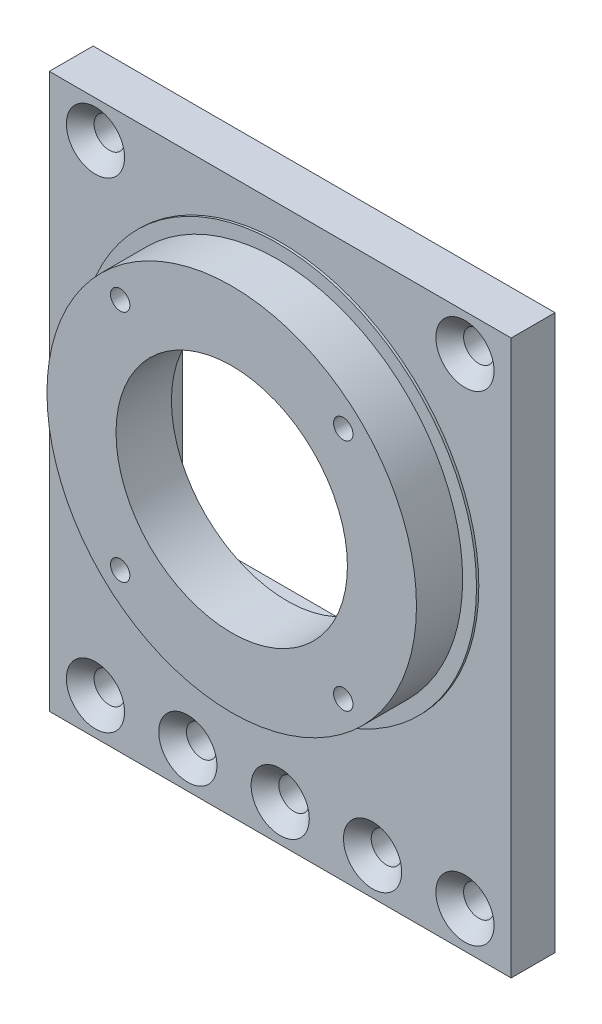
SolidWorks part; units mm, degrees
material "PVC rigide"
ref_plane "Plan de face" through (0, 0, 0) normal (0, 0, 1) x (1, 0, 0)
ref_plane "Plan de dessus" through (0, 0, 0) normal (0, 1, 0) x (1, 0, 0)
ref_plane "Plan de droite" through (0, 0, 0) normal (1, 0, 0) x (0, 0, -1)
sketch "Esquisse1" plane through (0, 0, 0) normal (0, 0, 1) x (1, 0, 0)
  line L1 (28, 28) -> (-28, 28)
  line L2 (28, 28) -> (28, -28)
  line L3 (28, -28) -> (-28, -28)
  line L4 (-28, 28) -> (-28, -28)
  line L5 (28, 28) -> (-28, -28) construction
  line L6 (28, -28) -> (-28, 28) construction
  line L7 (50, 50) -> (-50, 50)
  line L8 (50, 50) -> (50, -50)
  line L9 (50, -50) -> (-50, -50)
  line L10 (-50, 50) -> (-50, -50)
  line L11 (50, 50) -> (-50, -50) construction
  line L12 (50, -50) -> (-50, 50) construction
  circle A0 centre (0, 0) radius 40 construction
  point P0 (0, 0)
  dimension "D2" = 80
  dimension "D1" = 56
  dimension "D3" = 100
extrude "Boss.-Extru.1" add sketch "Esquisse1" along normal blind 10
fillet "Congé1" radius 3.5 4 edges at (-28, -28, 5) (28, 28, 5) (-28, 28, 5) (28, -28, 5)
sketch "Esquisse3" plane through (0, 0, 10) normal (0, 0, 1) x (1, 0, 0)
  line L5 (-28, 24.5) -> (-28, -24.5)
  line L6 (24.5, 28) -> (-24.5, 28)
  line L7 (28, -24.5) -> (28, 24.5)
  line L8 (-24.5, -28) -> (24.5, -28)
  line L9 (-28, 24.5) -> (-28, -24.5)
  line L10 (24.5, 28) -> (-24.5, 28)
  line L11 (28, -24.5) -> (28, 24.5)
  line L12 (-24.5, -28) -> (24.5, -28)
  circle A0 centre (0, 0) radius 40
  arc A5 (-24.5, 28) -> (-28, 24.5) centre (-24.5, 24.5) ccw
  arc A6 (28, 24.5) -> (24.5, 28) centre (24.5, 24.5) ccw
  arc A7 (24.5, -28) -> (28, -24.5) centre (24.5, -24.5) ccw
  arc A8 (-28, -24.5) -> (-24.5, -28) centre (-24.5, -24.5) ccw
  arc A9 (-24.5, 28) -> (-28, 24.5) centre (-24.5, 24.5) ccw
  arc A10 (28, 24.5) -> (24.5, 28) centre (24.5, 24.5) ccw
  arc A11 (24.5, -28) -> (28, -24.5) centre (24.5, -24.5) ccw
  arc A12 (-28, -24.5) -> (-24.5, -28) centre (-24.5, -24.5) ccw
  dimension "D1" = 80
  dimension "D2" = 0
extrude "Boss.-Extru.2" add sketch "Esquisse3" along normal blind 10
sketch "Esquisse4" plane through (0, 0, 10) normal (0, 0, 1) x (1, 0, 0)
  circle A0 centre (0, 0) radius 43
  circle A1 centre (0, 0) radius 40 construction
  dimension "D1" = 3
extrude "Enlèv. mat.-Extru.2" cut sketch "Esquisse4" against normal blind 0.5 flip side to cut
sketch "Esquisse5" plane through (0, 0, 0) normal (0, 0, -1) x (-1, 0, 0)
  line L1 (30.65, -30.65) -> (-30.65, -30.65)
  line L2 (30.65, -30.65) -> (30.65, 30.65)
  line L3 (30.65, 30.65) -> (-30.65, 30.65)
  line L4 (-30.65, -30.65) -> (-30.65, 30.65)
  line L5 (30.65, -30.65) -> (-30.65, 30.65) construction
  line L6 (30.65, 30.65) -> (-30.65, -30.65) construction
  point P0 (0, 0)
  dimension "D1" = 61.3
extrude "Enlèv. mat.-Extru.3" cut sketch "Esquisse5" against normal blind 9
sketch "Esquisse6" plane through (0, 0, 9) normal (0, 0, -1) x (-1, 0, 0)
  line L4 (-30.65, 30.65) -> (-30.65, -30.65)
  line L5 (-30.65, -30.65) -> (30.65, -30.65)
  line L6 (30.65, -30.65) -> (30.65, 30.65)
  line L7 (30.65, 30.65) -> (-30.65, 30.65)
  line L8 (-30.65, 30.65) -> (-30.65, -30.65)
  line L9 (-30.65, -30.65) -> (30.65, -30.65)
  line L10 (30.65, -30.65) -> (30.65, 30.65)
  line L11 (30.65, 30.65) -> (-30.65, 30.65)
  line L13 (28, -24.5) -> (28, 24.5)
  line L14 (-24.5, -28) -> (24.5, -28)
  line L15 (-28, 24.5) -> (-28, -24.5)
  line L16 (24.5, 28) -> (-24.5, 28)
  line L17 (28, -24.5) -> (28, 24.5)
  line L18 (-24.5, -28) -> (24.5, -28)
  line L19 (-28, 24.5) -> (-28, -24.5)
  line L20 (24.5, 28) -> (-24.5, 28)
  arc A4 (28, 24.5) -> (24.5, 28) centre (24.5, 24.5) ccw
  arc A5 (24.5, -28) -> (28, -24.5) centre (24.5, -24.5) ccw
  arc A6 (-28, -24.5) -> (-24.5, -28) centre (-24.5, -24.5) ccw
  arc A7 (-24.5, 28) -> (-28, 24.5) centre (-24.5, 24.5) ccw
  arc A8 (28, 24.5) -> (24.5, 28) centre (24.5, 24.5) ccw
  arc A9 (24.5, -28) -> (28, -24.5) centre (24.5, -24.5) ccw
  arc A10 (-28, -24.5) -> (-24.5, -28) centre (-24.5, -24.5) ccw
  arc A11 (-24.5, 28) -> (-28, 24.5) centre (-24.5, 24.5) ccw
  dimension "D1" = 0
  dimension "D2" = 0
extrude "Boss.-Extru.3" add sketch "Esquisse6" along normal blind 1
sketch "Esquisse12" plane through (0, -50, 0) normal (0, -1, 0) x (1, 0, 0)
  line L4 (50, 9.5) -> (-50, 9.5)
  line L5 (-50, 9.5) -> (-50, 0)
  line L6 (-50, 0) -> (50, 0)
  line L7 (50, 0) -> (50, 9.5)
  line L8 (50, 9.5) -> (-50, 9.5)
  line L9 (-50, 9.5) -> (-50, 0)
  line L10 (-50, 0) -> (50, 0)
  line L11 (50, 0) -> (50, 9.5)
  dimension "D1" = 0
extrude "Boss.-Extru.5" add sketch "Esquisse12" along normal blind 20
sketch "Esquisse7" plane through (0, 0, 8) normal (0, 0, -1) x (-1, 0, 0)
  line L5 (-24.5, -28) -> (24.5, -28)
  line L6 (28, -24.5) -> (28, 24.5)
  line L7 (24.5, 28) -> (-24.5, 28)
  line L8 (-28, 24.5) -> (-28, -24.5)
  line L9 (-24.5, -28) -> (24.5, -28)
  line L10 (28, -24.5) -> (28, 24.5)
  line L11 (24.5, 28) -> (-24.5, 28)
  line L12 (-28, 24.5) -> (-28, -24.5)
  circle A0 centre (0, 0) radius 25.05
  arc A5 (24.5, -28) -> (28, -24.5) centre (24.5, -24.5) ccw
  arc A6 (28, 24.5) -> (24.5, 28) centre (24.5, 24.5) ccw
  arc A7 (-24.5, 28) -> (-28, 24.5) centre (-24.5, 24.5) ccw
  arc A8 (-28, -24.5) -> (-24.5, -28) centre (-24.5, -24.5) ccw
  arc A9 (24.5, -28) -> (28, -24.5) centre (24.5, -24.5) ccw
  arc A10 (28, 24.5) -> (24.5, 28) centre (24.5, 24.5) ccw
  arc A11 (-24.5, 28) -> (-28, 24.5) centre (-24.5, 24.5) ccw
  arc A12 (-28, -24.5) -> (-24.5, -28) centre (-24.5, -24.5) ccw
  dimension "D1" = 50.1
  dimension "D2" = 0
extrude "Boss.-Extru.4" add sketch "Esquisse7" against normal up to surface (12 mm away) up to face at (40, 0, 20)
sketch "Esquisse10" plane through (0, 0, 8) normal (0, 0, -1) x (-1, 0, 0)
  line L1 (-24.1504, -25.3329) -> (24.1504, -25.3329) construction
  line L2 (-24.1504, -25.3329) -> (-24.1504, 25.3329) construction
  line L3 (-24.1504, 25.3329) -> (24.1504, 25.3329) construction
  line L4 (24.1504, -25.3329) -> (24.1504, 25.3329) construction
  line L5 (-24.1504, -25.3329) -> (24.1504, 25.3329) construction
  line L6 (-24.1504, 25.3329) -> (24.1504, -25.3329) construction
  circle A0 centre (0, 0) radius 35 construction
  point P0 (0, 0)
  dimension "D1" = 70
hole_wizard "Trou taraudé M5x0.81" positions "Esquisse3D2" profile "Esquisse11" tap size "M5x0.8" standard "Ansi Metric" end condition through all
sketch3d "Esquisse3D2"
  point P0 (24.1504, 25.3329, 8)
  point P3 (24.1504, -25.3329, 8)
  point P6 (-24.1504, 25.3329, 8)
  point P9 (-24.1504, -25.3329, 8)
sketch "Esquisse11" plane through (24.1504, 25.3329, 8) normal (1, 0, 0) x (0, 1, 0)
  line L0 (0, 0) -> (0, 12)
  line L1 (0, 12) -> (2.1, 12)
  line L2 (2.1, 12) -> (2.1, 0)
  line L5 (2.1, 0) -> (0, 0)
  line L11 (0, -6.35) -> (0, 107.95) construction
  dimension "Diamètre principal du filetage" = 4.2
  dimension "Profondeur du trou pour taraudage jusqu'au prochain" = 12
sketch "Esquisse13" plane through (0, 0, 9.5) normal (0, 0, 1) x (1, 0, 0)
  line L0 (-50, -62) -> (50, -62) construction
  line L1 (-50, 50) -> (-50, -70) construction
  line L2 (50, -70) -> (50, 50) construction
  line L3 (50, -70) -> (-50, -70) construction
  line L4 (0, -62) -> (0, -70) construction
  line L5 (-40, -62) -> (-40, -70) construction
  line L6 (40, -62) -> (40, -70) construction
  line L7 (-20, -62) -> (-20, -70) construction
  line L8 (20, -62) -> (20, -70) construction
  line L9 (-50, 42) -> (50, 42) construction
  line L10 (50, 50) -> (-50, 50) construction
  line L11 (-40, -62) -> (-40, 50) construction
  line L12 (40, -62) -> (40, 50) construction
  dimension "D1" = 8
  dimension "D2" = 10
  dimension "D3" = 20
  dimension "D4" = 8
hole_wizard "Fraisage pour vis à tête fraisée M61" positions "Esquisse3D3" profile "Esquisse14" countersink size "M6" standard "Ansi Metric" end condition through all
sketch3d "Esquisse3D3"
  line L0 (-40, -62, 9.5) -> (-40, -70, 9.5) construction
  line L1 (-50, 42, 9.5) -> (50, 42, 9.5) construction
  line L2 (40, -62, 9.5) -> (40, 50, 9.5) construction
  line L3 (-40, -62, 9.5) -> (-40, 50, 9.5) construction
  point P0 (-40, -62, 9.5)
  point P4 (-20, -62, 9.5)
  point P7 (0, -62, 9.5)
  point P10 (20, -62, 9.5)
  point P13 (40, -62, 9.5)
  point P21 (-40, 42, 9.5)
  point P25 (40, 42, 9.5)
sketch "Esquisse14" plane through (-40, -62, 9.5) normal (1, 0, 0) x (0, -1, 0)
  line L0 (0, 0) -> (0, 9.5)
  line L1 (0, 9.5) -> (3.3, 9.5)
  line L2 (3.3, 9.5) -> (3.3, 3)
  line L3 (3.3, 3) -> (6.3, 0)
  line L5 (6.3, 0) -> (0, 0)
  line L6 (-3.3, 3) -> (-6.3, 0) construction
  line L11 (0, -6.35) -> (0, 107.95) construction
  dimension "Diamètre du perçage jusqu'au prochain" = 6.6
  dimension "Profondeur du perçage jusqu'au prochain" = 9.5
  dimension "Diamètre du fraisage entrant" = 12.6
  dimension "Angle du fraisage entrant" = 90
fillet "Congé2" radius 4 4 edges at (-30.65, 30.65, 4) (-30.65, -30.65, 4) (30.65, 30.65, 4) (30.65, -30.65, 4)
